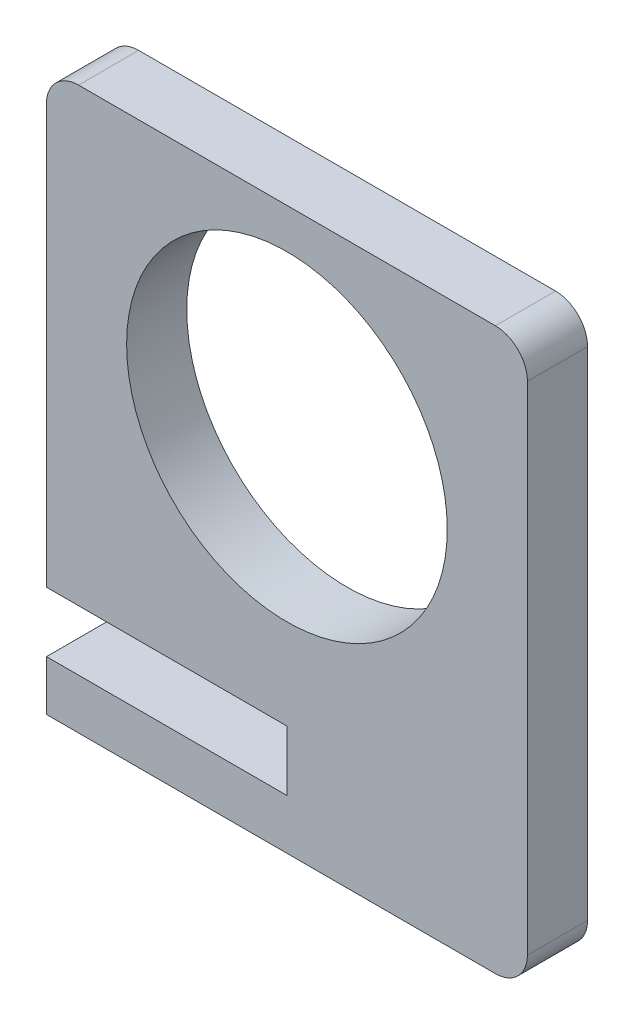
SolidWorks part; units mm, degrees
ref_plane "Front Plane" through (0, 0, 0) normal (0, 0, 1) x (1, 0, 0)
ref_plane "Top Plane" through (0, 0, 0) normal (0, 1, 0) x (1, 0, 0)
ref_plane "Right Plane" through (0, 0, 0) normal (1, 0, 0) x (0, 0, -1)
sketch "Sketch1" plane through (0, 0, 0) normal (0, 0, 1) x (1, 0, 0)
  line L0 (-19.05, 2.3813) -> (-19.05, 6.35)
  line L1 (-19.05, -2.3813) -> (0, -2.3813)
  line L3 (-19.05, 2.3813) -> (0, 2.3813)
  line L4 (0, -2.3813) -> (0, 2.3813)
  line L5 (-19.05, 6.35) -> (19.05, 6.35)
  line L6 (0, 0) -> (19.05, 0) construction
  line L7 (19.05, 6.35) -> (19.05, -6.35)
  line L8 (-19.05, -6.35) -> (19.05, -6.35)
  line L9 (-19.05, -2.3813) -> (-19.05, -6.35)
  line L10 (-19.05, 38.1) -> (19.05, 6.35) construction
  line L11 (-19.05, 6.35) -> (19.05, 6.35)
  line L12 (-19.05, 6.35) -> (-19.05, 38.1)
  line L13 (-19.05, 38.1) -> (19.05, 38.1)
  line L14 (19.05, 6.35) -> (19.05, 38.1)
  line L15 (19.05, 38.1) -> (-19.05, 6.35) construction
  circle A0 centre (0, 22.225) radius 12.7
  dimension "D6" = 25.4
  dimension "D1" = 19.05
  dimension "D2" = 4.7625
  dimension "D3" = 19.05
  dimension "D4" = 12.7
  dimension "D5" = 44.45
extrude "Boss-Extrude1" add sketch "Sketch1" along normal mid plane 4.7625 contours L5 L14 L13 L12 | L6 L4 L1 L9 L8 L7 | L4 L6 L7 L5 L0 L3 region at (2.1981, 0, 0) region at (-18.554, 22.225, 0)
fillet "Fillet1" radius 2.54 3 edges at (19.05, -6.35, 0) (-19.05, 38.1, 0) (19.05, 38.1, 0)
equation "\"D2@Sketch1\"=\"thick@FullAssem.Assembly\""
equation "\"D1@Sketch2\"=\"rodThick@FullAssem.Assembly\""
equation "\"D1@Boss-Extrude1\"=\"thick@FullAssem.Assembly\""
